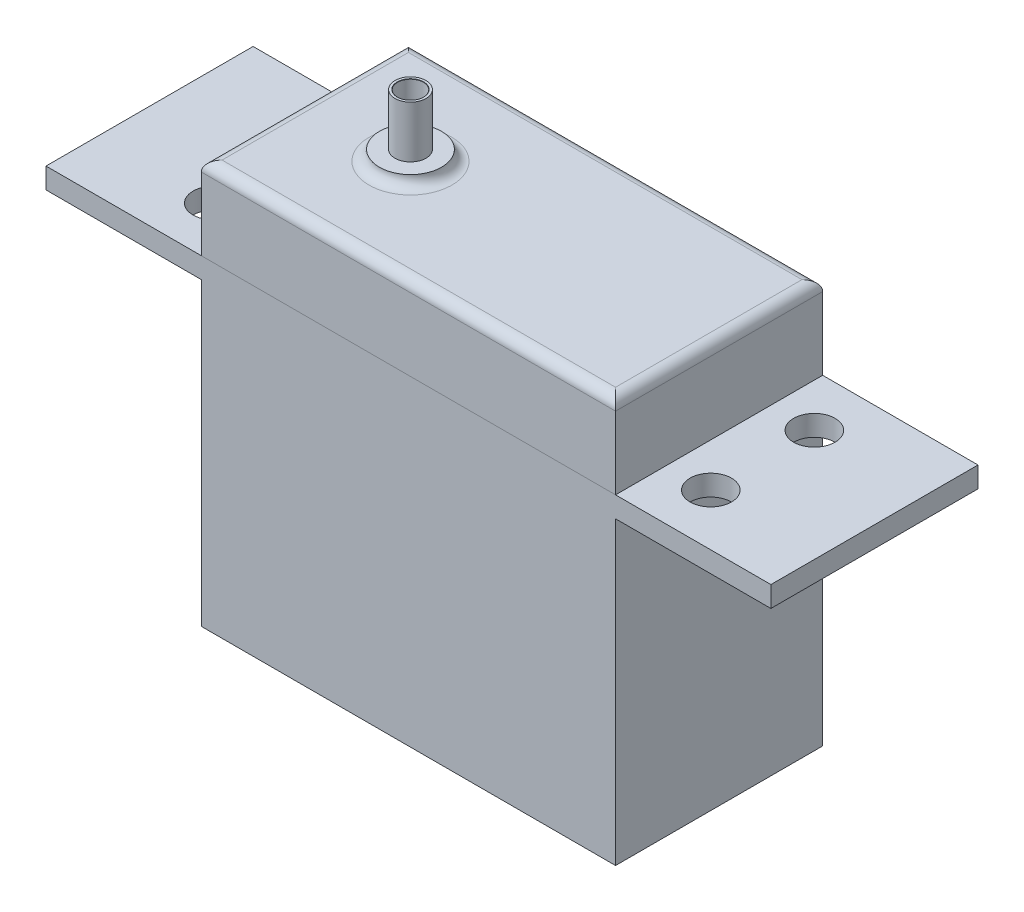
SolidWorks part; units mm, degrees
ref_plane "前视基准面" through (0, 0, 0) normal (0, 0, 1) x (1, 0, 0)
ref_plane "上视基准面" through (0, 0, 0) normal (0, 1, 0) x (1, 0, 0)
ref_plane "右视基准面" through (0, 0, 0) normal (1, 0, 0) x (0, 0, -1)
other "Configuration Table"
sketch "草图1" plane through (0, 0, 0) normal (0, 0, 1) x (1, 0, 0)
  line L1 (20, -19.5) -> (-20, -19.5)
  line L2 (20, -19.5) -> (20, 19.5)
  line L3 (20, 19.5) -> (-20, 19.5)
  line L4 (-20, -19.5) -> (-20, 19.5)
  line L5 (20, -19.5) -> (-20, 19.5) construction
  line L6 (20, 19.5) -> (-20, -19.5) construction
  point P0 (0, 0)
  point P5 (0, 0)
  dimension "D1" = 40
  dimension "D2" = 39
extrude "凸台-拉伸1" add sketch "草图1" along normal blind 20 contours L3 L4 L1 L2
sketch "草图2" plane through (-20, 0, 0) normal (-1, 0, 0) x (0, 0, 1)
  line L0 (0, 11.5) -> (0, 9.5)
  line L1 (0, -19.5) -> (0, 19.5) construction
  line L2 (0, 11.5) -> (20, 11.5)
  line L3 (20, -19.5) -> (20, 19.5) construction
  line L4 (0, 9.5) -> (20, 9.5)
  line L5 (20, 11.5) -> (20, 9.5)
  dimension "D2" = 2
extrude "凸台-拉伸2" add sketch "草图2" along normal blind 15 contours L2 L5 L4 L0
sketch "草图6" plane through (20, 0, 0) normal (1, 0, 0) x (0, 0, -1)
  line L0 (-20, 11.5) -> (0, 11.5)
  line L1 (0, -19.5) -> (0, 19.5) construction
  line L2 (0, 11.5) -> (0, 9.5)
  line L3 (-20, 11.5) -> (-20, 9.5)
  line L4 (-20, 9.5) -> (0, 9.5)
  dimension "D1" = 2
extrude "凸台-拉伸3" add sketch "草图6" along normal blind 15 contours L0 L2 L4 L3
sketch "草图7" plane through (0, 0, 0) normal (0, 0, -1) x (-1, 0, 0)
  point P0 (20, -19.5)
sketch "草图8" plane through (0, 11.5, 0) normal (0, 1, 0) x (1, 0, 0)
  circle A0 centre (-23.8042, -5) radius 2
  circle A1 centre (-23.8042, -15) radius 2
  circle A2 centre (24.1958, -5) radius 2
  circle A3 centre (24.1958, -15) radius 2
  dimension "D1" = 4
  dimension "D3" = 4
  dimension "D2" = 10
  dimension "D4" = 10
  dimension "D5" = 48
sketch "草图9" plane through (0, 11.5, 0) normal (0, 1, 0) x (1, 0, 0)
sketch "草图10" plane through (0, 11.5, 0) normal (0, 1, 0) x (1, 0, 0)
sketch "草图11" plane through (0, 19.5, 0) normal (0, 1, 0) x (1, 0, 0)
  circle A0 centre (-9.8042, -10) radius 3
  dimension "D1" = 6
  dimension "D2" = 14
extrude "切除-拉伸1" cut sketch "草图8" against normal blind 6 contours A0 | A1 | A2 | A3
sketch "草图14" plane through (0, 0, 20) normal (0, 0, 1) x (1, 0, 0)
  line L0 (-20, 11.5) -> (20, 11.5)
  line L1 (16.6206, 9.4438) -> (16.7132, 9.5494)
  line L3 (9.4994, 0.7515) -> (9.403, 0.6958)
  point P6 (0, 0)
  point P7 (0, 0)
  point P10 (0, 0)
sketch "草图15" plane through (0, 0, 0) normal (0, 0, -1) x (-1, 0, 0)
  line L0 (-20, 11.5) -> (20, 11.5)
split line "分割线1"
split line "分割线2"
extrude "凸台-拉伸5" add sketch "草图11" along normal blind 1 contours A0
sketch "草图16" plane through (0, 20.5, 0) normal (0, 1, 0) x (1, 0, 0)
  circle A0 centre (-9.8042, -10) radius 1.5
  point P2 (-9.8137, -10.0023)
  point P3 (0, 0)
  point P4 (-9.8042, -10)
  dimension "D1" = 3
extrude "凸台-拉伸7" add sketch "草图16" along normal blind 5
sketch "草图25" plane through (0, 25.5, 0) normal (0, 1, 0) x (1, 0, 0)
  point P0 (-9.8042, -10)
hole_wizard "M3 螺纹孔的螺纹孔钻头3" positions "草图25" profile "草图26" hole size "M3" standard "ISO"
sketch "草图26" plane through (-9.8042, 25.5, 10) normal (1, 0, 0) x (0, 0, 1)
  line L0 (0, 0) -> (0, 3.7511)
  line L1 (0, 3.7511) -> (1.25, 3)
  line L2 (1.25, 3) -> (1.25, 0.025)
  line L3 (1.25, 0.025) -> (1.275, 0)
  line L5 (1.275, 0) -> (0, 0)
  line L6 (-1.25, 0.025) -> (-1.275, 0) construction
  line L10 (0, 3.7511) -> (-1.25, 3) construction
  line L11 (0, -6.35) -> (0, 107.95) construction
  dimension "孔直径" = 2.5
  dimension "孔深度" = 3
  dimension "近端锥形沉头孔直径" = 2.55
  dimension "近端锥形沉头孔角度" = 90
  dimension "导头角度" = 118
fillet "圆角4" radius 1 5 edges at (20, 19.5, 10) (0, 19.5, 20) (-20, 19.5, 10) (0, 19.5, 0) (-9.8042, 19.5, 7)
